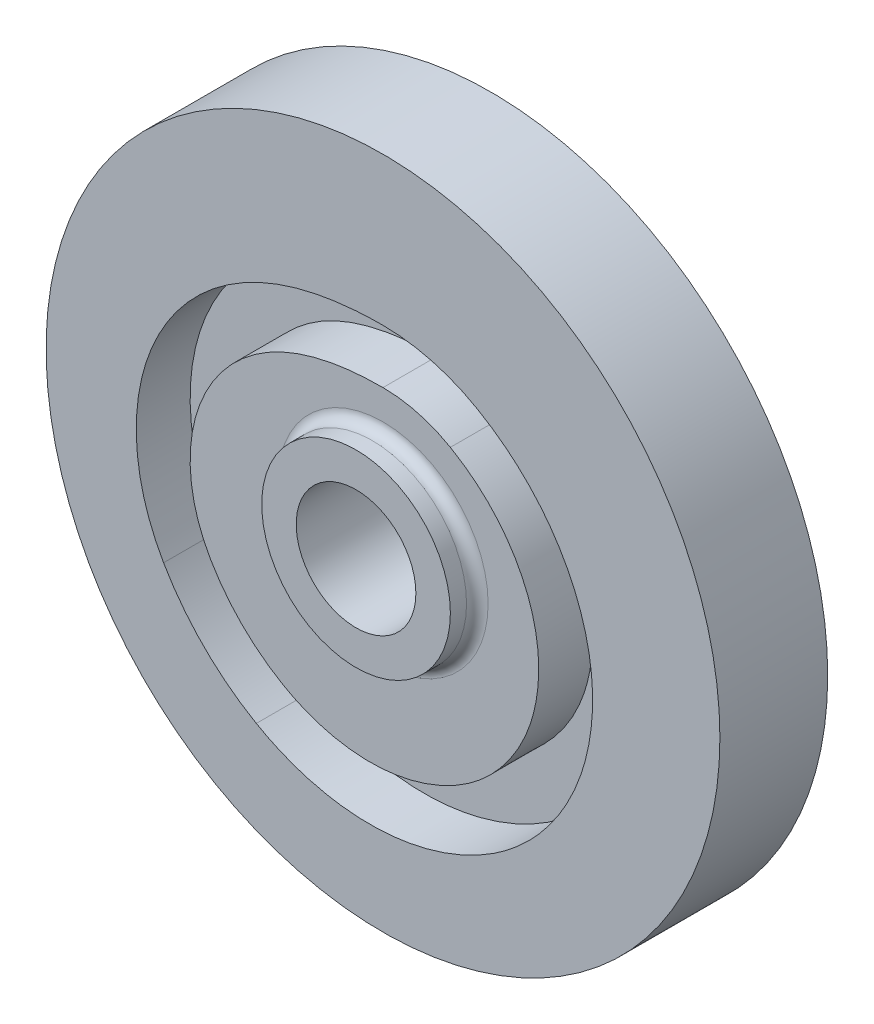
SolidWorks part; units mm, degrees
note: The reader was unsure of these and kept them because the rebuilt part matched: shared geometry of "草圖1<3>".
ref_plane "前基準面" through (0, 0, 0) normal (0, 0, 1) x (1, 0, 0)
ref_plane "上基準面" through (0, 0, 0) normal (0, 1, 0) x (1, 0, 0)
ref_plane "右基準面" through (0, 0, 0) normal (1, 0, 0) x (0, 0, -1)
sketch "草圖1" plane through (0, 0, 0) normal (0, 0, 1) x (1, 0, 0)
  line L0 (0, 0) -> (0, 16.0468) construction
  circle A0 centre (0, 0) radius 62.5
  circle A1 centre (0, 0) radius 17.5
  circle A3 centre (0, 0) radius 11.1
  point P11 (0, 13.3148)
  dimension "D1" = 125
  dimension "D2" = 35
  dimension "D3" = 22.2
extrude "伸長1" add sketch "草圖1" along normal blind 20 contours A0 A1
extrude "伸長2" add sketch "草圖1<3>" along normal blind 25
sketch "草圖1<3>" plane through (0, 0, 0) normal (0, 0, 1) x (1, 0, 0) same geometry as "草圖1"
fillet "圓角1" radius 2 1 edges at (17.5, 0, 20)
sketch "草圖2" plane through (0, 0, 20) normal (0, 0, 1) x (1, 0, 0)
  line L0 (0, 0) -> (0, 67.9374) construction
  line L1 (0, 0) -> (35.1798, 60.9331) construction
  line L2 (0, 0) -> (-44.106, -76.3939) construction
  line L3 (0, 0) -> (-71.4412, -41.2466) construction
  line L4 (18, 31.1769) -> (23.1962, 34.1769) construction
  line L5 (18, 31.1769) -> (23.1962, 28.1769) construction
  line L6 (18, 31.1769) -> (24, 31.1769) construction
  line L7 (18, 31.1769) -> (21, 25.9808) construction
  line L8 (18, 31.1769) -> (18, 25.1769) construction
  line L9 (0, 0) -> (44.534, 25.7117) construction
  line L10 (0, 0) -> (58.8728, 0) construction
  line L11 (0, 0) -> (41.0325, -23.6901) construction
  line L12 (0, 0) -> (23.2436, -40.2591) construction
  line L13 (0, 0) -> (0, -43.7629) construction
  line L14 (0, 0) -> (-51.866, 29.9449) construction
  line L15 (0, 0) -> (-17.972, 49.3777) construction
  line L16 (0, 0) -> (-35.2088, 41.9602) construction
  line L17 (0, 0) -> (-58.0188, 10.2303) construction
  line L18 (0, 0) -> (-58.1936, -10.2611) construction
  circle A0 centre (0, 0) radius 30 construction
  circle A1 centre (0, 0) radius 42 construction
  arc A2 (15, 25.9808) -> (0, 30) centre (0, 0) ccw
  arc A3 (-36.3731, -21) -> (-21, -36.3731) centre (0, 0) ccw
  circle A4 centre (18, 31.1769) radius 6 construction
  arc A5 (18, 25.1769) -> (26.8031, 15.4748) centre (0, 0) cw construction
  arc A6 (21, 25.9808) -> (33.4066, 0) centre (0, 0) cw construction
  arc A7 (23.1962, 28.1769) -> (31.607, -18.2483) centre (0, 0) cw construction
  arc A8 (24, 31.1769) -> (19.6723, -34.0735) centre (0, 0) cw construction
  arc A9 (23.1962, 34.1769) -> (0, -41.3052) centre (0, 0) cw construction
  arc A10 (18, 25.1769) -> (-10.5854, 29.0831) centre (0, 0) ccw construction
  arc A11 (21, 25.9808) -> (-21.4733, 25.5909) centre (0, 0) ccw construction
  arc A12 (23.1962, 28.1769) -> (-31.607, 18.2483) centre (0, 0) ccw construction
  arc A13 (24, 31.1769) -> (-38.7469, 6.8321) centre (0, 0) ccw construction
  arc A14 (23.1962, 34.1769) -> (-40.6777, -7.1726) centre (0, 0) ccw construction
  arc A15 (-40.7032, -23.5) -> (-23.5, -40.7032) centre (0, 0) ccw
  arc A16 (17.5, 30.3109) -> (0, 35) centre (0, 0) ccw
  arc A17 (-32.0429, -18.5) -> (-18.5, -32.0429) centre (0, 0) ccw
  arc A18 (12.5, 21.6506) -> (0, 25) centre (0, 0) ccw
  spline S0 degree 3 poles (15, 25.9808) (19.6263, 23.3097) (27.9629, 15.9473) (35.0026, -0.2371) (33.1239, -19.3581) (20.5869, -35.9342) (-0.1181, -43.44) (-14.5917, -40.0729) (-21, -36.3731) knots 0 0 0 0 0.139448 0.287926 0.449748 0.624667 0.809633 1 1 1 1
  spline S1 degree 3 poles (-36.3731, -21) (-38.8267, -16.7501) (-41.7284, -7.3892) (-39.7609, 6.9723) (-32.4417, 18.615) (-22.0709, 26.0281) (-10.9108, 29.436) (-3.5513, 30) (0, 30) knots 0 0 0 0 0.188917 0.373337 0.548989 0.712236 0.861397 1 1 1 1
  spline S2 degree 1 poles (17.5, 30.3109) (-23.5, -40.7032) knots 0 0 1 1 construction
  spline S3 degree 1 poles (-40.7032, -23.5) (0, 35) knots 0 0 1 1 construction
  spline S4 degree 3 poles (17.5, 30.3109) (19.8231, 28.9697) (24.2422, 25.8608) (31.7675, 18.1593) (36.9579, 8.4424) (39.0235, -2.3475) (38.8727, -10.5602) (37.0942, -18.5933) (33.6798, -26.107) (28.8614, -32.7441) (20.7773, -40.1901) (10.7417, -44.9035) (-0.0341, -46.5846) (-8.1851, -46.2416) (-14.7977, -44.6614) (-19.864, -42.6479) (-22.3128, -41.3887) (-23.5, -40.7032) knots 0 0 0 0 0.0625 0.125 0.25 0.3125 0.375 0.4375 0.5 0.5625 0.625 0.75 0.8125 0.875 0.9375 0.96875 1 1 1 1
  spline S5 degree 3 poles (-40.7032, -23.5) (-41.6335, -21.8887) (-43.2611, -18.5156) (-45.476, -11.4367) (-46.2437, -2.108) (-43.9025, 8.8975) (-38.4635, 18.7287) (-30.4814, 26.5586) (-20.7612, 31.8418) (-12.0984, 34.0777) (-5.1631, 34.8819) (-1.7246, 35) (0, 35) knots 0 0 0 0 0.0625 0.125 0.25 0.375 0.5 0.625 0.75 0.875 0.9375 1 1 1 1
  spline S6 degree 1 poles (12.5, 21.6506) (-18.5, -32.0429) knots 0 0 1 1 construction
  spline S7 degree 1 poles (-32.0429, -18.5) (0, 25) knots 0 0 1 1 construction
  spline S8 degree 3 poles (12.5, 21.6506) (14.3001, 20.6114) (17.7365, 18.1923) (22.0574, 13.7663) (25.4699, 8.5891) (27.8349, 2.8372) (28.9862, -3.1849) (28.8761, -9.3779) (27.5357, -15.4159) (24.9902, -21.0218) (21.3323, -26.0626) (16.7758, -30.2594) (11.4508, -33.4507) (5.5502, -35.5777) (-0.604, -36.5366) (-6.7921, -36.2749) (-12.8485, -34.8333) (-16.6922, -33.0867) (-18.5, -32.0429) knots 0 0 0 0 0.0625 0.125 0.1875 0.25 0.3125 0.375 0.4375 0.5 0.5625 0.625 0.6875 0.75 0.8125 0.875 0.9375 1 1 1 1
  spline S9 degree 3 poles (-32.0429, -18.5) (-32.7282, -17.3132) (-33.9271, -14.8284) (-35.558, -9.6152) (-36.1196, -2.7666) (-34.4003, 5.3486) (-30.3881, 12.5918) (-25.4695, 17.423) (-20.7941, 20.417) (-15.7677, 22.768) (-10.2068, 24.2257) (-4.4423, 24.8973) (-1.4746, 25) (0, 25) knots 0 0 0 0 0.0625 0.125 0.25 0.375 0.5 0.625 0.6875 0.75 0.875 0.9375 1 1 1 1
  dimension "D1" = 60
  dimension "D2" = 84
  dimension "D3" = 30
  dimension "D4" = 30
  dimension "D5" = 30
  dimension "D6" = 20
  dimension "D7" = 20
  dimension "D8" = 20
  dimension "D9" = 20
  dimension "D10" = 5
  dimension "D11" = 5
extrude "伸長3" cut sketch "草圖2" against normal blind 10 contours S5 A15 S4 A16 A3 S1 A2 S0 | S1 A3 S0 A2 A17 S9 A18 S8
